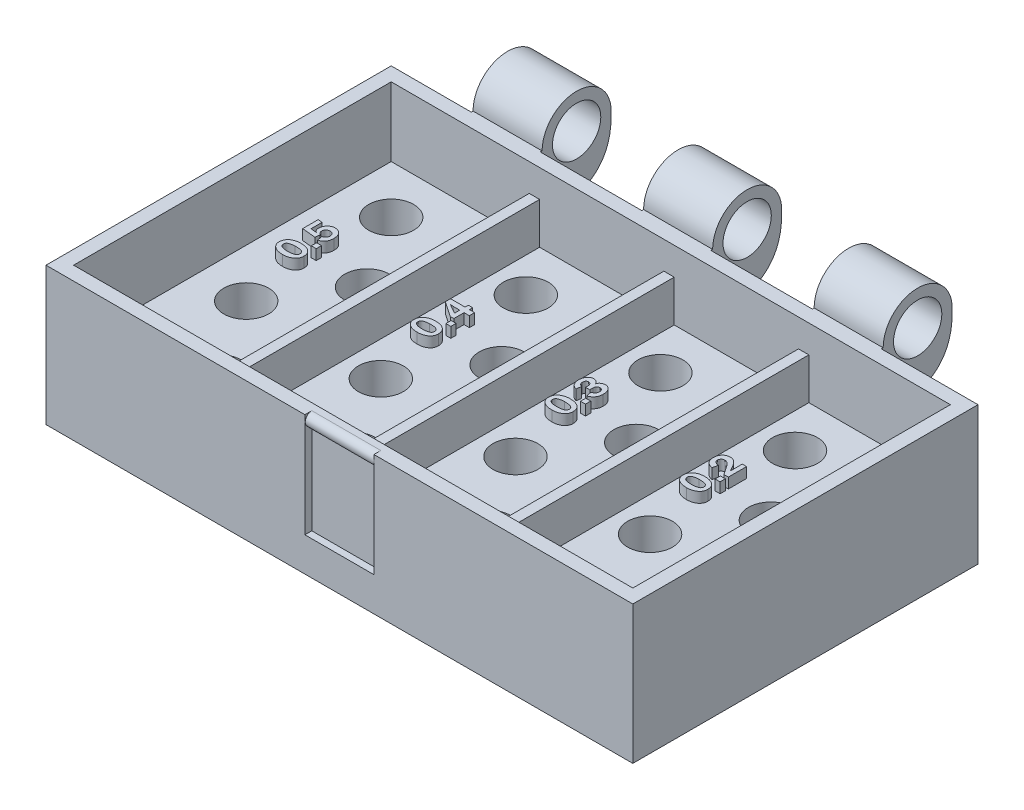
SolidWorks part; units mm, degrees
ref_plane "Plan de face" through (0, 0, 0) normal (0, 0, 1) x (1, 0, 0)
ref_plane "Plan de dessus" through (0, 0, 0) normal (0, 1, 0) x (1, 0, 0)
ref_plane "Plan de droite" through (0, 0, 0) normal (1, 0, 0) x (0, 0, -1)
sketch "Esquisse1" plane through (0, 0, 0) normal (0, 1, 0) x (1, 0, 0)
  line L1 (-42.5, 25) -> (42.5, 25)
  line L2 (-42.5, 25) -> (-42.5, -25)
  line L3 (-42.5, -25) -> (42.5, -25)
  line L4 (42.5, 25) -> (42.5, -25)
  line L5 (-42.5, 25) -> (42.5, -25) construction
  line L6 (-42.5, -25) -> (42.5, 25) construction
  point P0 (0, 0)
  dimension "D1" = 85
  dimension "D2" = 50
extrude "Boss.-Extru.1" add sketch "Esquisse1" along normal blind 20
shell "Coque1" thickness 2 removed face at (0, 20, 0)
sketch "Esquisse2" plane through (0, 10, 0) normal (0, 1, 0) x (1, 0, 0)
  line L0 (40.5, 23) -> (-40.5, 23) construction
  line L1 (-40.5, 23) -> (-40.5, -23) construction
  line L2 (-40.5, -23) -> (40.5, -23) construction
  line L3 (-40.5, 23) -> (-40.5, -23) construction
  circle A0 centre (-33.5, 16) radius 3.25
  circle A1 centre (-26.5, 5.5) radius 3.25
  circle A2 centre (-33.5, -5) radius 3.25
  circle A3 centre (-26.5, -16) radius 3.25
  dimension "D1" = 6.5
  dimension "D2" = 7
  dimension "D3" = 7
  dimension "D4" = 7
  dimension "D5" = 7
  dimension "D6" = 10.5
  dimension "D7" = 10.5
  dimension "D8" = 14
  dimension "D9" = 14
extrude "Enlèv. mat.-Extru.1" cut sketch "Esquisse2" against normal blind 6 contours A1 | A3 | A2 | A0 region at (-26.5, 10, -5.5) region at (-33.5, 10, 5) region at (-26.5, 10, 16)
pattern_linear "Répétition linéaire1" count 4 spacing 19.5 along (1, 0, 0) of "Enlèv. mat.-Extru.1"
sketch "Esquisse3" plane through (0, 10, 0) normal (0, 1, 0) x (1, 0, 0)
  line L0 (40.5, 23) -> (-40.5, 23) construction
  line L1 (-20.5, 23) -> (-19, 23)
  line L2 (-20.5, 23) -> (-20.5, -23)
  line L3 (-20.5, -23) -> (-19, -23)
  line L4 (-19, 23) -> (-19, -23)
  line L5 (-40.5, -23) -> (40.5, -23) construction
  line L6 (-40.5, 23) -> (-40.5, -23) construction
  dimension "D1" = 1.5
  dimension "D2" = 20
extrude "Boss.-Extru.2" add sketch "Esquisse3" along normal blind 6 contours L2 L3 L4 L1
pattern_linear "Répétition linéaire2" count 3 spacing 19.5 along (1, 0, 0) of "Boss.-Extru.2"
sketch "Esquisse6" plane through (0, 10, 0) normal (0, 1, 0) x (1, 0, 0)
  text T0 "0.5" font "Franklin Gothic Medium" height 3.5
  text T1 "0.4" font "Franklin Gothic Medium" height 3.5
  text T2 "0.3" font "Franklin Gothic Medium" height 3.5
  text T3 "0.2" font "Franklin Gothic Medium" height 3.5
extrude "Boss.-Extru.4" add sketch "Esquisse6" along normal blind 1.5
ref_plane "Plan1" through (18.5, 0, 0) normal (1, 0, 0) x (0, 0, -1)
sketch "Esquisse7" plane through (18.5, 0, 0) normal (1, 0, 0) x (0, 0, -1)
  line L0 (-25, 20) -> (25, 20) construction
  line L1 (25, 20) -> (25, 0) construction
  line L2 (25.2612, 20) -> (25, 20)
  line L3 (25, 20) -> (25, 11.3828)
  circle A0 centre (30.2612, 20) radius 5
  spline S0 degree 2 poles (35.2612, 20) (35.6074, 10.8736) (25, 11.3828) knots 0 0 0 1 1 1
  dimension "D1" = 0
  dimension "D2" = 10
extrude "Boss.-Extru.5" add sketch "Esquisse7" along normal blind 10 contours A0 | S0 A0 L2 L3 region at (18.5, 14.2539, -28.9071) region at (18.5, 20, -30.2612)
sketch "Esquisse8" plane through (28.5, 0, 0) normal (1, 0, 0) x (0, 0, -1)
  circle A0 centre (30.2612, 20) radius 3.5
  arc A1 (35.2612, 20) -> (25.2612, 20) centre (30.2612, 20) ccw construction
  dimension "D1" = 7
  dimension "D2" = 0
extrude "Enlèv. mat.-Extru.2" cut sketch "Esquisse8" against normal up to surface (10 mm away) up to face at (18.5, 20.1729, -28.9132)
pattern_linear "Répétition linéaire4" count 3 spacing 24.7 along (-1, 0, 0) of "Enlèv. mat.-Extru.2", "Boss.-Extru.5"
ref_plane "Plan2" through (0, 0, 0) normal (-1, 0, 0) x (0, 0, 1)
sketch "Esquisse9" plane through (0, 0, 0) normal (-1, 0, 0) x (0, 0, 1)
  line L1 (24, 18.0947) -> (24, 4.9263)
  line L2 (24, 4.9263) -> (25, 4.9263)
  line L3 (25, 20) -> (25, 0) construction
  line L4 (25, 4.9263) -> (25, 20)
  line L5 (25, 20) -> (24, 20)
  line L6 (-25, 20) -> (25, 20) construction
  arc A0 (24, 20) -> (24, 18.0947) centre (24, 19.0473) cw
  dimension "D1" = 1
  dimension "D2" = 1
  dimension "D3" = 0
  dimension "D4" = 1.9053
extrude "Enlèv. mat.-Extru.3" cut sketch "Esquisse9" against normal blind 5 and the other way blind 5
